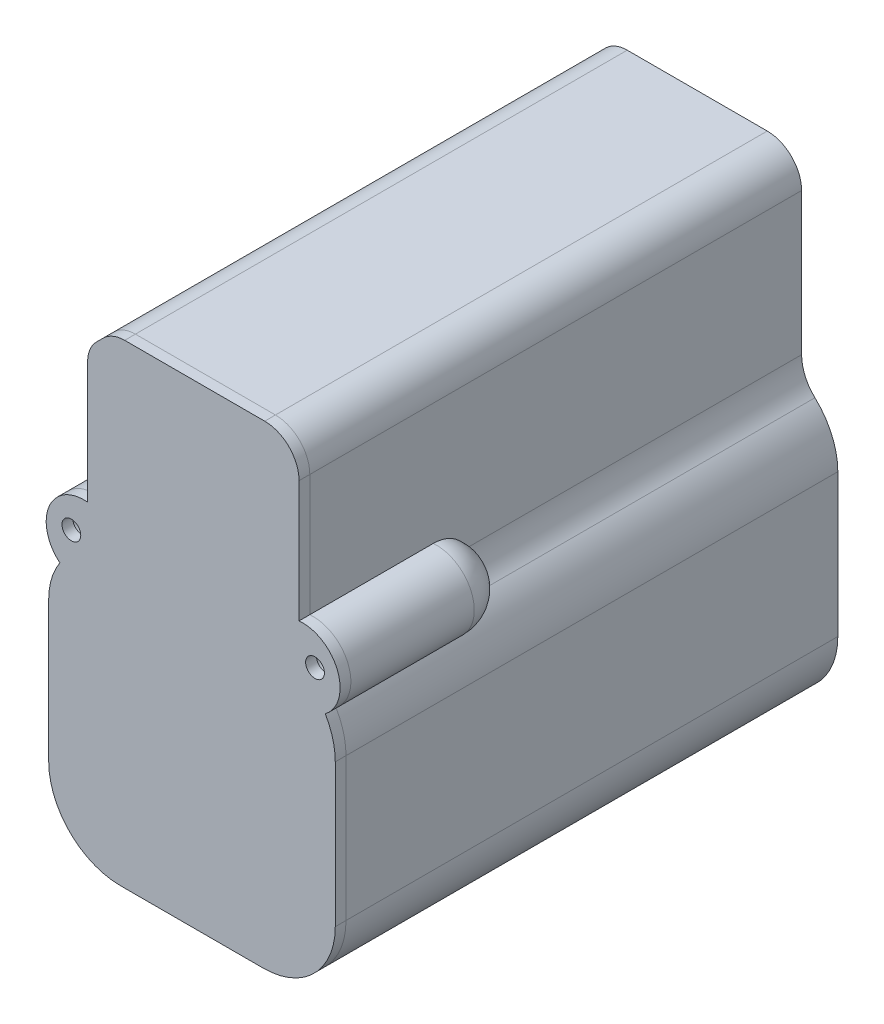
SolidWorks part; units mm, degrees
ref_plane "Front Plane" through (0, 0, 0) normal (0, 0, 1) x (1, 0, 0)
ref_plane "Top Plane" through (0, 0, 0) normal (0, 1, 0) x (1, 0, 0)
ref_plane "Right Plane" through (0, 0, 0) normal (1, 0, 0) x (0, 0, -1)
sketch "Sketch1" plane through (0, 0, 0) normal (0, 0, 1) x (1, 0, 0)
  line L1 (35, -50) -> (-35, -50)
  line L2 (35, -50) -> (35, 50)
  line L3 (35, 50) -> (-35, 50)
  line L4 (-35, -50) -> (-35, 50)
  line L5 (35, -50) -> (-35, 50) construction
  line L6 (35, 50) -> (-35, -50) construction
  point P0 (0, 0)
  dimension "D1" = 70
  dimension "D2" = 100
extrude "Boss-Extrude1" add sketch "Sketch1" along normal blind 2
sketch "Sketch2" plane through (0, 0, 0) normal (0, 0, -1) x (-1, 0, 0)
  line L0 (-17.2536, 39.8) -> (-17.2536, 13.2) construction
  line L1 (-13.0536, 9) -> (13.5464, 9) construction
  line L2 (17.7464, 13.2) -> (17.7464, 39.293) construction
  line L3 (16.7213, 41.7677) -> (15.5141, 42.9749) construction
  line L4 (13.0394, 44) -> (-13.0536, 44) construction
  line L5 (-17.2536, 39.8) -> (-17.2536, 13.3092) construction
  line L6 (-13.0536, 9) -> (13.5464, 9)
  line L7 (17.7464, 12.9384) -> (17.7464, 39.293) construction
  line L8 (16.7213, 41.7677) -> (15.5141, 42.9749) construction
  line L9 (13.0394, 44) -> (-13.0536, 44) construction
  line L10 (-24, -2.2) -> (-24, -28.8) construction
  line L11 (-12.8, -40) -> (13.8, -40) construction
  line L12 (25, -28.8) -> (25, -2.707) construction
  line L13 (21.9246, 4.7175) -> (20.7175, 5.9247) construction
  line L14 (13.2928, 9) -> (-12.8, 9) construction
  line L15 (-24, -2.2) -> (-24, -28.8) construction
  line L16 (-12.8, -40) -> (13.8, -40) construction
  line L17 (25, -28.8) -> (25, -2.707) construction
  line L18 (21.9246, 4.7175) -> (20.7175, 5.9247)
  line L19 (13.2928, 9) -> (-12.8, 9)
  line L20 (-17.4536, 39.8) -> (-17.4536, 13.3092)
  line L21 (13.0394, 44.2) -> (-13.0536, 44.2)
  line L22 (16.8627, 41.9092) -> (15.6556, 43.1163)
  line L23 (17.9464, 12.9384) -> (17.9464, 39.293)
  line L24 (25.2, -28.8) -> (25.2, -2.707)
  line L25 (-12.8, -40.2) -> (13.8, -40.2)
  line L26 (-24.2, -2.2) -> (-24.2, -28.8)
  line L27 (-26.2, -2.2) -> (-26.2, -28.8)
  line L28 (-12.8, -42.2) -> (13.8, -42.2)
  line L29 (27.2, -28.8) -> (27.2, -2.707)
  line L30 (19.9464, 12.9384) -> (19.9464, 39.293)
  line L31 (18.2769, 43.3234) -> (17.0698, 44.5306)
  line L32 (13.0393, 46.2) -> (-13.0536, 46.2)
  line L33 (-19.4536, 39.8) -> (-19.4536, 13.3092)
  arc A0 (-13.0536, 44) -> (-17.2536, 39.8) centre (-13.0536, 39.8) ccw construction
  arc A1 (-17.2536, 13.2) -> (-13.0536, 9) centre (-13.0536, 13.2) ccw construction
  arc A2 (13.5464, 9) -> (17.7464, 13.2) centre (13.5464, 13.2) ccw construction
  arc A3 (17.7464, 39.293) -> (16.7213, 41.7677) centre (14.2466, 39.293) ccw construction
  arc A4 (15.5141, 42.9749) -> (13.0394, 44) centre (13.0394, 40.5002) ccw construction
  arc A5 (-13.0536, 44) -> (-17.2536, 39.8) centre (-13.0536, 39.8) ccw construction
  arc A6 (-17.2536, 13.2) -> (-13.0536, 9) centre (-13.0536, 13.2) ccw
  arc A7 (13.5464, 9) -> (17.7464, 13.2) centre (13.5464, 13.2) ccw
  arc A8 (17.7464, 39.293) -> (16.7213, 41.7677) centre (14.2466, 39.293) ccw construction
  arc A9 (15.5141, 42.9749) -> (13.0394, 44) centre (13.0394, 40.5002) ccw construction
  arc A10 (-24, -28.8) -> (-12.8, -40) centre (-12.8, -28.8) ccw construction
  arc A11 (13.8, -40) -> (25, -28.8) centre (13.8, -28.8) ccw construction
  arc A12 (25, -2.707) -> (21.9246, 4.7175) centre (14.5002, -2.707) ccw construction
  arc A13 (20.7175, 5.9247) -> (13.2928, 9) centre (13.293, -1.4998) ccw construction
  arc A14 (-12.8, 9) -> (-24, -2.2) centre (-12.8, -2.2) ccw construction
  arc A15 (-24, -28.8) -> (-12.8, -40) centre (-12.8, -28.8) ccw construction
  arc A16 (13.8, -40) -> (25, -28.8) centre (13.8, -28.8) ccw construction
  arc A17 (25, -2.707) -> (21.2848, 5.3064) centre (14.5002, -2.707) ccw construction
  arc A18 (20.7175, 5.9247) -> (13.2928, 9) centre (13.293, -1.4998) ccw
  arc A19 (-20.4359, 5.9935) -> (-24, -2.2) centre (-12.8, -2.2) ccw construction
  arc A20 (21.2848, 5.3064) -> (17.7464, 12.9384) centre (27.7464, 12.9384) cw construction
  arc A21 (-20.4359, 5.9935) -> (-17.2536, 13.3092) centre (-27.2536, 13.3092) ccw construction
  arc A22 (-20.5722, 6.1398) -> (-17.4536, 13.3092) centre (-27.2536, 13.3092) ccw
  arc A23 (-13.0536, 44.2) -> (-17.4536, 39.8) centre (-13.0536, 39.8) ccw
  arc A24 (15.6556, 43.1163) -> (13.0394, 44.2) centre (13.0394, 40.5002) ccw
  arc A25 (17.9464, 39.293) -> (16.8627, 41.9092) centre (14.2466, 39.293) ccw
  arc A26 (21.414, 5.4591) -> (17.9464, 12.9384) centre (27.7464, 12.9384) cw
  arc A27 (25.2, -2.707) -> (21.414, 5.4591) centre (14.5002, -2.707) ccw
  arc A28 (13.8, -40.2) -> (25.2, -28.8) centre (13.8, -28.8) ccw
  arc A29 (-24.2, -28.8) -> (-12.8, -40.2) centre (-12.8, -28.8) ccw
  arc A30 (-20.5722, 6.1398) -> (-24.2, -2.2) centre (-12.8, -2.2) ccw
  arc A31 (-21.9358, 7.603) -> (-26.2, -2.2) centre (-12.8, -2.2) ccw
  arc A32 (-26.2, -28.8) -> (-12.8, -42.2) centre (-12.8, -28.8) ccw
  arc A33 (13.8, -42.2) -> (27.2, -28.8) centre (13.8, -28.8) ccw
  arc A34 (27.2, -2.707) -> (22.7063, 6.9855) centre (14.5002, -2.707) ccw
  arc A35 (22.7063, 6.9855) -> (19.9464, 12.9384) centre (27.7464, 12.9384) cw
  arc A36 (19.9464, 39.293) -> (18.2769, 43.3234) centre (14.2466, 39.293) ccw
  arc A37 (17.0698, 44.5306) -> (13.0393, 46.2) centre (13.0394, 40.5002) ccw
  arc A38 (-13.0536, 46.2) -> (-19.4536, 39.8) centre (-13.0536, 39.8) ccw
  arc A39 (-21.9358, 7.603) -> (-19.4536, 13.3092) centre (-27.2536, 13.3092) ccw
  line M23 (35, -50) -> (35, 50)
  line M24 (35, 50) -> (-35, 50)
  line M25 (-35, 50) -> (-35, -50)
  line M26 (-35, -50) -> (35, -50)
  dimension "D1" = 10
  dimension "D2" = 0.2
  dimension "D3" = 2
extrude "Cut-Extrude1" cut sketch "Sketch2" against normal up to next contours A31 A39 L33 A38 L32 A37 L31 A36 L30 A35 A34 L29 A33 L28 A32 L27 M26 M23 M24 M25 region at (0, -48.7793, 0)
sketch "Sketch3" plane through (0, 0, 0) normal (0, 0, -1) x (-1, 0, 0)
  line L0 (-19.4536, 39.8) -> (-19.4536, 13.3092) construction
  line L1 (-26.2, -2.2) -> (-26.2, -28.8) construction
  line L2 (-12.8, -42.2) -> (13.8, -42.2) construction
  line L3 (27.2, -28.8) -> (27.2, -2.707) construction
  line L4 (19.9464, 12.9384) -> (19.9464, 39.293) construction
  line L5 (18.2769, 43.3234) -> (17.0698, 44.5306) construction
  line L6 (13.0393, 46.2) -> (-13.0536, 46.2) construction
  line L7 (-19.4536, 39.8) -> (-19.4536, 13.3092)
  line L8 (-26.2, -2.2) -> (-26.2, -28.8)
  line L9 (-12.8, -42.2) -> (13.8, -42.2)
  line L10 (27.2, -28.8) -> (27.2, -2.707)
  line L11 (19.9464, 12.9384) -> (19.9464, 39.293)
  line L12 (18.2769, 43.3234) -> (17.0698, 44.5306)
  line L13 (13.0393, 46.2) -> (-13.0536, 46.2)
  arc A0 (-13.0536, 46.2) -> (-19.4536, 39.8) centre (-13.0536, 39.8) ccw construction
  arc A1 (-21.9358, 7.603) -> (-19.4536, 13.3092) centre (-27.2536, 13.3092) ccw construction
  arc A2 (-21.9358, 7.603) -> (-26.2, -2.2) centre (-12.8, -2.2) ccw construction
  arc A3 (-26.2, -28.8) -> (-12.8, -42.2) centre (-12.8, -28.8) ccw construction
  arc A4 (13.8, -42.2) -> (27.2, -28.8) centre (13.8, -28.8) ccw construction
  arc A5 (27.2, -2.707) -> (22.7063, 6.9855) centre (14.5002, -2.707) ccw construction
  arc A6 (19.9464, 12.9384) -> (22.7063, 6.9855) centre (27.7464, 12.9384) ccw construction
  arc A7 (19.9464, 39.293) -> (18.2769, 43.3234) centre (14.2466, 39.293) ccw construction
  arc A8 (17.0698, 44.5306) -> (13.0393, 46.2) centre (13.0394, 40.5002) ccw construction
  arc A9 (-13.0536, 46.2) -> (-19.4536, 39.8) centre (-13.0536, 39.8) ccw
  arc A10 (-21.9358, 7.603) -> (-19.4536, 13.3092) centre (-27.2536, 13.3092) ccw
  arc A11 (-21.9358, 7.603) -> (-26.2, -2.2) centre (-12.8, -2.2) ccw
  arc A12 (-26.2, -28.8) -> (-12.8, -42.2) centre (-12.8, -28.8) ccw
  arc A13 (13.8, -42.2) -> (27.2, -28.8) centre (13.8, -28.8) ccw
  arc A14 (27.2, -2.707) -> (22.7063, 6.9855) centre (14.5002, -2.707) ccw
  arc A15 (19.9464, 12.9384) -> (22.7063, 6.9855) centre (27.7464, 12.9384) ccw
  arc A16 (19.9464, 39.293) -> (18.2769, 43.3234) centre (14.2466, 39.293) ccw
  arc A17 (17.0698, 44.5306) -> (13.0393, 46.2) centre (13.0394, 40.5002) ccw
extrude "Extrude-Thin1" add sketch "Sketch3" against normal offset from surface (91.6373 mm away) 1.2 thin offset beyond the face yes thin type one direction reverse wall 2
sketch "Sketch4" plane through (0, 0, 91.6373) normal (0, 0, 1) x (1, 0, 0)
  line L0 (-19.9464, 12.9384) -> (-19.9464, 39.293) construction
  line L1 (-19.9464, 16.6201) -> (-25.1214, 4.2553) construction
  line L2 (-20.67, 9.6576) -> (-27.1272, 12.3601) construction
  line L10 (13.0536, 46.2) -> (-13.0394, 46.2)
  line L11 (-17.0698, 44.5306) -> (-18.277, 43.3233)
  line L12 (-19.9464, 39.293) -> (-19.9464, 12.9384)
  line L13 (-27.2, -2.707) -> (-27.2, -28.8)
  line L14 (-13.8, -42.2) -> (12.8, -42.2)
  line L15 (26.2, -28.8) -> (26.2, -2.2)
  line L16 (19.4536, 13.3092) -> (19.4536, 39.8)
  line L19 (-19.9464, 16.6201) -> (-19.9464, 12.9384)
  arc A0 (-19.9464, 16.6201) -> (-25.1214, 4.2553) centre (-20.67, 9.6576) ccw
  arc A1 (-22.7063, 6.9855) -> (-19.9464, 12.9384) centre (-27.7464, 12.9384) ccw construction
  arc A2 (-22.7063, 6.9855) -> (-27.2, -2.707) centre (-14.5002, -2.707) ccw construction
  arc A14 (19.4536, 39.8) -> (13.0536, 46.2) centre (13.0536, 39.8) ccw
  arc A15 (-13.0394, 46.2) -> (-17.0698, 44.5306) centre (-13.0394, 40.5002) ccw
  arc A16 (-18.277, 43.3233) -> (-19.9464, 39.293) centre (-14.2466, 39.293) ccw
  arc A17 (-22.7063, 6.9855) -> (-19.9464, 12.9384) centre (-27.7464, 12.9384) ccw
  arc A18 (-22.7063, 6.9855) -> (-27.2, -2.707) centre (-14.5002, -2.707) ccw
  arc A19 (-27.2, -28.8) -> (-13.8, -42.2) centre (-13.8, -28.8) ccw
  arc A20 (12.8, -42.2) -> (26.2, -28.8) centre (12.8, -28.8) ccw
  arc A21 (26.2, -2.2) -> (21.9358, 7.603) centre (12.8, -2.2) ccw
  arc A22 (19.4536, 13.3092) -> (21.9358, 7.603) centre (27.2536, 13.3092) ccw
  arc A26 (-22.7063, 6.9855) -> (-19.9464, 12.9384) centre (-27.7464, 12.9384) ccw
  arc A27 (-22.7063, 6.9855) -> (-25.1214, 4.2553) centre (-14.5002, -2.707) ccw
  dimension "D1" = 7
extrude "Boss-Extrude2" add sketch "Sketch4" against normal blind 30
sketch "Sketch5" plane through (0, 0, 91.6373) normal (0, 0, 1) x (1, 0, 0)
  line L0 (-19.9464, 16.6201) -> (-25.1214, 4.2553) construction
  line L1 (-18.8555, 8.8164) -> (-27.0906, 12.4462) construction
  arc A0 (-21.414, 5.4591) -> (-17.9464, 12.9384) centre (-27.7464, 12.9384) ccw construction
  arc A1 (-19.9464, 16.6201) -> (-25.1214, 4.2553) centre (-20.67, 9.6576) ccw construction
  circle A2 centre (-22.973, 10.6313) radius 2.3
  point P12 (-22.5339, 10.4377)
  point P15 (-22.973, 10.6313)
  dimension "D1" = 4.6
extrude "Cut-Extrude2" cut sketch "Sketch5" against normal blind 7
sketch "Sketch14" plane through (0, 0, 91.6373) normal (0, 0, 1) x (1, 0, 0)
  circle A0 centre (-22.973, 10.6313) radius 1.75
  dimension "D1" = 3.5
extrude "Cut-Extrude8" cut sketch "Sketch14" against normal blind 24
fillet "Fillet1" radius 7 1 edges at (-27.1272, 12.3601, 61.6373)
sketch "Sketch6" plane through (0, 0, 91.6373) normal (0, 0, 1) x (1, 0, 0)
  line L0 (19.4536, 39.8) -> (19.4536, 13.3092) construction
  line L8 (-19.9464, 39.293) -> (-19.9464, 16.6201)
  line L9 (-27.2, -2.707) -> (-27.2, -28.8)
  line L10 (-13.8, -42.2) -> (12.8, -42.2)
  line L11 (26.2, -28.8) -> (26.2, -2.2)
  line L12 (19.4536, 13.3092) -> (19.4536, 39.8)
  line L13 (13.0536, 46.2) -> (-13.0394, 46.2)
  line L14 (-17.0698, 44.5306) -> (-18.277, 43.3233)
  line L19 (19.4536, 13.3092) -> (19.4536, 17.1678)
  arc A0 (19.4536, 17.1678) -> (24.3333, 4.6222) centre (20.101, 10.1978) cw
  arc A1 (19.4536, 13.3092) -> (21.9358, 7.603) centre (27.2536, 13.3092) ccw construction
  arc A2 (26.2, -2.2) -> (21.9358, 7.603) centre (12.8, -2.2) ccw construction
  arc A12 (-19.9464, 16.6201) -> (-25.1214, 4.2553) centre (-20.67, 9.6576) ccw
  arc A13 (-25.1214, 4.2553) -> (-27.2, -2.707) centre (-14.5002, -2.707) ccw
  arc A14 (-27.2, -28.8) -> (-13.8, -42.2) centre (-13.8, -28.8) ccw
  arc A15 (12.8, -42.2) -> (26.2, -28.8) centre (12.8, -28.8) ccw
  arc A16 (26.2, -2.2) -> (21.9358, 7.603) centre (12.8, -2.2) ccw
  arc A17 (19.4536, 13.3092) -> (21.9358, 7.603) centre (27.2536, 13.3092) ccw
  arc A18 (19.4536, 39.8) -> (13.0536, 46.2) centre (13.0536, 39.8) ccw
  arc A19 (-13.0394, 46.2) -> (-17.0698, 44.5306) centre (-13.0394, 40.5002) ccw
  arc A20 (-18.277, 43.3233) -> (-19.9464, 39.293) centre (-14.2466, 39.293) ccw
  arc A25 (24.3333, 4.6222) -> (21.9358, 7.603) centre (12.8, -2.2) ccw
  arc A26 (19.4536, 13.3092) -> (21.9358, 7.603) centre (27.2536, 13.3092) ccw
  dimension "D1" = 7
extrude "Boss-Extrude3" add sketch "Sketch6" against normal blind 30
fillet "Fillet3" radius 7 1 edges at (26.6249, 12.7353, 61.6373)
sketch "Sketch7" plane through (0, 0, 91.6373) normal (0, 0, 1) x (1, 0, 0)
  line L0 (19.4536, 17.1678) -> (24.3333, 4.6222) construction
  line L1 (18.267, 9.4) -> (26.5873, 12.83) construction
  arc A0 (17.4536, 13.3092) -> (20.5722, 6.1398) centre (27.2536, 13.3092) ccw construction
  arc A1 (24.3333, 4.6222) -> (19.4536, 17.1678) centre (20.101, 10.1978) ccw construction
  circle A2 centre (22.4271, 11.115) radius 2.3
  point P12 (21.8934, 10.895)
  point P16 (22.4271, 11.115)
  dimension "D1" = 4.6
extrude "Cut-Extrude3" cut sketch "Sketch7" against normal blind 7
sketch "Sketch15" plane through (0, 0, 91.6373) normal (0, 0, 1) x (1, 0, 0)
  circle A0 centre (22.4271, 11.115) radius 1.75
  dimension "D1" = 3.5
extrude "Cut-Extrude9" cut sketch "Sketch15" against normal blind 24
sketch "Sketch9" plane through (0, 0, 0) normal (0, 0, -1) x (-1, 0, 0)
  line L28 (13.7464, 15) -> (13.7464, 38)
  line L29 (11.7464, 40) -> (-11.2536, 40)
  line L30 (-13.2536, 38) -> (-13.2536, 15)
  line L31 (-11.2536, 13) -> (11.7464, 13)
  line L32 (13.7464, 15) -> (13.7464, 38)
  line L33 (11.7464, 40) -> (-11.2536, 40)
  line L34 (-13.2536, 38) -> (-13.2536, 15)
  line L35 (-11.2536, 13) -> (11.7464, 13)
  line L52 (-12.8, -36) -> (13.8, -36)
  line L53 (21, -28.8) -> (21, -2.707)
  line L54 (19.0962, 1.8891) -> (17.889, 3.0962)
  line L55 (13.2929, 5) -> (-12.8, 5)
  line L56 (-20, -2.2) -> (-20, -28.8)
  line L57 (-12.8, -36) -> (13.8, -36)
  line L58 (21, -28.8) -> (21, -2.707)
  line L59 (19.0962, 1.8891) -> (17.889, 3.0962)
  line L60 (13.2929, 5) -> (-12.8, 5)
  line L61 (-20, -2.2) -> (-20, -28.8)
  arc A28 (11.7464, 13) -> (13.7464, 15) centre (11.7464, 15) ccw
  arc A29 (13.7464, 38) -> (11.7464, 40) centre (11.7464, 38) ccw
  arc A30 (-11.2536, 40) -> (-13.2536, 38) centre (-11.2536, 38) ccw
  arc A31 (-13.2536, 15) -> (-11.2536, 13) centre (-11.2536, 15) ccw
  arc A32 (11.7464, 13) -> (13.7464, 15) centre (11.7464, 15) ccw
  arc A33 (13.7464, 38) -> (11.7464, 40) centre (11.7464, 38) ccw
  arc A34 (-11.2536, 40) -> (-13.2536, 38) centre (-11.2536, 38) ccw
  arc A35 (-13.2536, 15) -> (-11.2536, 13) centre (-11.2536, 15) ccw
  arc A52 (-20, -28.8) -> (-12.8, -36) centre (-12.8, -28.8) ccw
  arc A53 (13.8, -36) -> (21, -28.8) centre (13.8, -28.8) ccw
  arc A54 (21, -2.707) -> (19.0962, 1.8891) centre (14.5002, -2.707) ccw
  arc A55 (17.889, 3.0962) -> (13.2929, 5) centre (13.293, -1.4998) ccw
  arc A56 (-12.8, 5) -> (-20, -2.2) centre (-12.8, -2.2) ccw
  arc A57 (-20, -28.8) -> (-12.8, -36) centre (-12.8, -28.8) ccw
  arc A58 (13.8, -36) -> (21, -28.8) centre (13.8, -28.8) ccw
  arc A59 (21, -2.707) -> (19.0962, 1.8891) centre (14.5002, -2.707) ccw
  arc A60 (17.889, 3.0962) -> (13.2929, 5) centre (13.293, -1.4998) ccw
  arc A61 (-12.8, 5) -> (-20, -2.2) centre (-12.8, -2.2) ccw
  dimension "D1" = 1
  dimension "D2" = 1
extrude "Cut-Extrude4" cut sketch "Sketch9" against normal up to next
sketch "Sketch10" plane through (0, 0, 91.6373) normal (0, 0, 1) x (1, 0, 0)
  line L0 (26.2, -2.2) -> (26.2, -28.8) construction
  line L1 (12.8, -42.2) -> (-13.8, -42.2) construction
  line L2 (-27.2, -28.8) -> (-27.2, -2.707) construction
  line L3 (19.4536, 39.8) -> (19.4536, 17.1678) construction
  line L4 (-13.0393, 46.2) -> (13.0536, 46.2) construction
  line L5 (-18.2769, 43.3234) -> (-17.0698, 44.5306) construction
  line L6 (-19.9464, 16.6201) -> (-19.9464, 39.293) construction
  line L7 (26.2, -2.2) -> (26.2, -28.8)
  line L8 (12.8, -42.2) -> (-13.8, -42.2)
  line L9 (-27.2, -28.8) -> (-27.2, -2.707)
  line L10 (19.4536, 39.8) -> (19.4536, 17.1678)
  line L11 (-13.0393, 46.2) -> (13.0536, 46.2)
  line L12 (-18.2769, 43.3234) -> (-17.0698, 44.5306)
  line L13 (-19.9464, 16.6201) -> (-19.9464, 39.293)
  arc A0 (-25.1214, 4.2553) -> (-27.2, -2.707) centre (-14.5002, -2.707) ccw construction
  arc A1 (26.2, -2.2) -> (24.3333, 4.6222) centre (12.8, -2.2) ccw construction
  arc A2 (12.8, -42.2) -> (26.2, -28.8) centre (12.8, -28.8) ccw construction
  arc A3 (-27.2, -28.8) -> (-13.8, -42.2) centre (-13.8, -28.8) ccw construction
  arc A4 (24.3333, 4.6222) -> (19.4536, 17.1678) centre (20.101, 10.1978) ccw construction
  arc A5 (-19.9464, 16.6201) -> (-25.1214, 4.2553) centre (-20.67, 9.6576) ccw construction
  arc A6 (19.4536, 39.8) -> (13.0536, 46.2) centre (13.0536, 39.8) ccw construction
  arc A7 (-13.0393, 46.2) -> (-17.0698, 44.5306) centre (-13.0394, 40.5002) ccw construction
  arc A8 (-18.2769, 43.3234) -> (-19.9464, 39.293) centre (-14.2466, 39.293) ccw construction
  arc A9 (-25.1214, 4.2553) -> (-27.2, -2.707) centre (-14.5002, -2.707) ccw
  arc A10 (26.2, -2.2) -> (24.3333, 4.6222) centre (12.8, -2.2) ccw
  arc A11 (12.8, -42.2) -> (26.2, -28.8) centre (12.8, -28.8) ccw
  arc A12 (-27.2, -28.8) -> (-13.8, -42.2) centre (-13.8, -28.8) ccw
  arc A13 (24.3333, 4.6222) -> (19.4536, 17.1678) centre (20.101, 10.1978) ccw
  arc A14 (-19.9464, 16.6201) -> (-25.1214, 4.2553) centre (-20.67, 9.6576) ccw
  arc A15 (19.4536, 39.8) -> (13.0536, 46.2) centre (13.0536, 39.8) ccw
  arc A16 (-13.0393, 46.2) -> (-17.0698, 44.5306) centre (-13.0394, 40.5002) ccw
  arc A17 (-18.2769, 43.3234) -> (-19.9464, 39.293) centre (-14.2466, 39.293) ccw
extrude "Boss-Extrude4" add sketch "Sketch10" along normal blind 2 separate body
sketch "Sketch11" plane through (0, 0, 93.6373) normal (0, 0, 1) x (1, 0, 0)
  circle A0 centre (-22.973, 10.6313) radius 1.75
  circle A1 centre (22.4271, 11.115) radius 1.75
  dimension "D1" = 3.5
  dimension "D2" = 3.5
extrude "Cut-Extrude5" cut sketch "Sketch11" against normal up to next (2 mm away)
sketch "Sketch12" plane through (-19.9464, 0, 0) normal (-1, 0, 0) x (0, 0, 1)
  line L0 (30.2675, 17.7465) -> (39.2675, 17.7465) construction
  line L1 (39.2675, 17.7465) -> (39.2675, 34.7465) construction
  line L2 (39.2675, 34.7465) -> (30.2675, 34.7465) construction
  line L3 (30.2675, 34.7465) -> (30.2675, 17.7465) construction
  line L4 (30.2675, 17.7465) -> (39.2675, 17.7465) construction
  line L5 (39.2675, 17.7465) -> (39.2675, 34.7465) construction
  line L6 (39.2675, 34.7465) -> (30.2675, 34.7465) construction
  line L7 (30.2675, 34.7465) -> (30.2675, 17.7465) construction
  line L8 (30.2675, 16.7465) -> (39.2675, 16.7465)
  line L9 (40.2675, 17.7465) -> (40.2675, 34.7465)
  line L10 (39.2675, 35.7465) -> (30.2675, 35.7465)
  line L11 (29.2675, 34.7465) -> (29.2675, 17.7465)
  line L12 (29.2675, 35.7465) -> (29.2675, 16.7465) construction
  line L13 (29.2675, 16.7465) -> (40.2675, 16.7465) construction
  line L14 (40.2675, 16.7465) -> (40.2675, 35.7465) construction
  line L15 (40.2675, 35.7465) -> (29.2675, 35.7465) construction
  arc A0 (29.2675, 17.7465) -> (30.2675, 16.7465) centre (30.2675, 17.7465) ccw
  arc A1 (40.2675, 17.7465) -> (39.2675, 16.7465) centre (39.2675, 17.7465) cw
  arc A2 (40.2675, 34.7465) -> (39.2675, 35.7465) centre (39.2675, 34.7465) ccw
  arc A3 (29.2675, 34.7465) -> (30.2675, 35.7465) centre (30.2675, 34.7465) cw
  dimension "D2" = 1
  dimension "D1" = 1
extrude "Cut-Extrude6" cut sketch "Sketch12" against normal up to next (2 mm away)
sketch "Sketch13" plane through (-27.2, 0, 0) normal (-1, 0, 0) x (0, 0, 1)
  line L0 (78.947, -24) -> (87.8341, -24) construction
  line L1 (87.8341, -24) -> (87.947, -7) construction
  line L2 (78.947, -7) -> (78.947, -24) construction
  line L3 (87.947, -7) -> (78.947, -7) construction
  line L4 (78.947, -24) -> (87.8341, -24) construction
  line L5 (87.8341, -24) -> (87.947, -7) construction
  line L6 (78.947, -7) -> (78.947, -24) construction
  line L7 (87.947, -7) -> (78.947, -7) construction
  line L8 (78.947, -25) -> (87.8341, -25)
  line L9 (88.8341, -24.0066) -> (88.9469, -7.0066)
  line L10 (87.947, -6) -> (78.947, -6)
  line L11 (77.947, -7) -> (77.947, -24)
  line L12 (77.947, -6) -> (77.947, -25) construction
  line L13 (77.947, -25) -> (88.8275, -25) construction
  line L14 (88.8275, -25) -> (88.9536, -6) construction
  line L15 (88.9536, -6) -> (77.947, -6) construction
  arc A0 (77.947, -24) -> (78.947, -25) centre (78.947, -24) ccw
  arc A1 (88.8341, -24.0066) -> (87.8341, -25) centre (87.8341, -24) cw
  arc A2 (88.9469, -7.0066) -> (87.947, -6) centre (87.947, -7) ccw
  arc A3 (77.947, -7) -> (78.947, -6) centre (78.947, -7) cw
  dimension "D2" = 1
  dimension "D1" = 1
extrude "Cut-Extrude7" cut sketch "Sketch13" against normal up to next (2 mm away)
sketch "Sketch16" plane through (0, 0, 91.6373) normal (0, 0, -1) x (-1, 0, 0)
  line L14 (-17.2536, 39.8) -> (-17.2536, 13.3092)
  line L15 (-24, -2.2) -> (-24, -28.8)
  line L16 (-12.8, -40) -> (13.8, -40)
  line L17 (25, -28.8) -> (25, -2.707)
  line L18 (17.7464, 12.9384) -> (17.7464, 39.293)
  line L19 (16.7213, 41.7677) -> (15.5141, 42.9749)
  line L20 (13.0393, 44) -> (-13.0536, 44)
  line L21 (-17.2536, 39.8) -> (-17.2536, 13.3092)
  line L22 (-24, -2.2) -> (-24, -28.8)
  line L23 (-12.8, -40) -> (13.8, -40)
  line L24 (25, -28.8) -> (25, -2.707)
  line L25 (17.7464, 12.9384) -> (17.7464, 39.293)
  line L26 (16.7213, 41.7677) -> (15.5141, 42.9749)
  line L27 (13.0393, 44) -> (-13.0536, 44)
  arc A18 (-13.0536, 44) -> (-17.2536, 39.8) centre (-13.0536, 39.8) ccw
  arc A19 (-20.4359, 5.9935) -> (-17.2536, 13.3092) centre (-27.2536, 13.3092) ccw
  arc A20 (-20.4359, 5.9935) -> (-24, -2.2) centre (-12.8, -2.2) ccw
  arc A21 (-24, -28.8) -> (-12.8, -40) centre (-12.8, -28.8) ccw
  arc A22 (13.8, -40) -> (25, -28.8) centre (13.8, -28.8) ccw
  arc A23 (25, -2.707) -> (21.2848, 5.3064) centre (14.5002, -2.707) ccw
  arc A24 (17.7464, 12.9384) -> (21.2848, 5.3064) centre (27.7464, 12.9384) ccw
  arc A25 (17.7464, 39.293) -> (16.7213, 41.7677) centre (14.2466, 39.293) ccw
  arc A26 (15.5141, 42.9749) -> (13.0393, 44) centre (13.0394, 40.5002) ccw
  arc A27 (-13.0536, 44) -> (-17.2536, 39.8) centre (-13.0536, 39.8) ccw
  arc A28 (-20.4359, 5.9935) -> (-17.2536, 13.3092) centre (-27.2536, 13.3092) ccw
  arc A29 (-20.4359, 5.9935) -> (-24, -2.2) centre (-12.8, -2.2) ccw
  arc A30 (-24, -28.8) -> (-12.8, -40) centre (-12.8, -28.8) ccw
  arc A31 (13.8, -40) -> (25, -28.8) centre (13.8, -28.8) ccw
  arc A32 (25, -2.707) -> (21.2848, 5.3064) centre (14.5002, -2.707) ccw
  arc A33 (17.7464, 12.9384) -> (21.2848, 5.3064) centre (27.7464, 12.9384) ccw
  arc A34 (17.7464, 39.293) -> (16.7213, 41.7677) centre (14.2466, 39.293) ccw
  arc A35 (15.5141, 42.9749) -> (13.0393, 44) centre (13.0394, 40.5002) ccw
  dimension "D1" = 0.2
extrude "Extrude-Thin2" add sketch "Sketch16" along normal blind 1 thin thin type one direction reverse wall 1
sketch "Sketch17" plane through (0, 0, 91.6373) normal (0, 0, -1) x (-1, 0, 0)
  line L2 (-17.2536, 13.2) -> (-17.2536, 39.8) construction
  line L3 (-13.0536, 44) -> (13.0394, 44) construction
  circle A0 centre (-0.0071, 26.5) radius 3
  point P4 (-17.2536, 26.5)
  point P7 (-0.0071, 44)
  dimension "D1" = 6
  dimension "D2" = 0
  dimension "D3" = 0
extrude "Boss-Extrude5" add sketch "Sketch17" along normal offset from surface (49.8373 mm away) 0.2
sketch "Sketch18" plane through (0, 0, 41.8) normal (0, 0, -1) x (-1, 0, 0)
  circle A0 centre (-0.0071, 26.5) radius 2
  dimension "D1" = 4
extrude "Cut-Extrude10" cut sketch "Sketch18" against normal offset from surface (47.8373 mm away) 2 up to face at (3.0071, 26.5, 91.6373)
equation "\"base_thickness\"= 2"
equation "\"front_thickness\"= 2"
equation "\"back_offset\"= 1.5"
equation "\"base_side_offset\"= 1"
equation "\"hole_inner_radius\"=2"
equation "\"snap_fit_thickness\"= 2"
equation "\"hole_outer_radius\"= 6"
equation "\"base_enclosure_camera_gap\"= 1"
equation "\"camera_front_enclosure_gap\"= 4"
equation "\"usb_hole_width\"= 9"
equation "\"usb_hole_length\"= 17"
equation "\"snap_fit_width\"= 6"
equation "\"snap_fit_base_length\"= 5.5"
equation "\"snap_fit_front_length\"= 7"
equation "\"snap_fit_height\"= 0.9"
equation "\"snap_fit_front_length_wide_cam\"= 8"
equation "\"D1@Boss-Extrude1\"=\"base_thickness\""
equation "\"outer_enclosure_offset\"= 0.2"
equation "\"D2@Sketch2\"=\"outer_enclosure_offset\""
equation "\"D3@Sketch2\"=\"base_thickness\""
equation "\"D5@Extrude-Thin1\"=\"base_thickness\""
equation "\"D1@Extrude-Thin1\"=\"outer_enclosure_offset\"+1"
equation "\"D1@Sketch5\"=\"thread_insert_d_outer_enclosure\"-0.4"
equation "\"D1@Sketch7\"=\"thread_insert_d_outer_enclosure\"-0.4"
equation "\"D1@Boss-Extrude4\"=\"base_thickness\""
equation "\"thread_insert_d_outer_enclosure\"= 5'outer inclosure thread insert diameter"
equation "\"screw_d_outer_enclousre\"= 3.5'diameter of screw outer enclosure"
equation "\"D1@Sketch4\"=\"thread_insert_d_outer_enclosure\"+2"
equation "\"D1@Fillet1\"=\"thread_insert_d_outer_enclosure\"+2"
equation "\"D1@Sketch6\"=\"thread_insert_d_outer_enclosure\"+2"
equation "\"D1@Fillet3\"=\"thread_insert_d_outer_enclosure\"+2"
equation "\"thread_insert_h_outer_enclosure\"= 5'outer enclosure thread insert height"
equation "\"screw_h_outer_enclosure\"= 23'outer_enclosure_screw_height"
equation "\"D1@Cut-Extrude2\"=\"thread_insert_h_outer_enclosure\"+2"
equation "\"D1@Sketch14\"=\"screw_d_outer_enclousre\""
equation "\"D1@Cut-Extrude8\"=\"screw_h_outer_enclosure\"+1"
equation "\"D1@Cut-Extrude3\"=\"thread_insert_h_outer_enclosure\"+2"
equation "\"D1@Sketch15\"=\"screw_d_outer_enclousre\""
equation "\"D1@Cut-Extrude9\"=\"screw_h_outer_enclosure\"+1"
equation "\"D1@Sketch11\"=\"screw_d_outer_enclousre\""
equation "\"D2@Sketch11\"=\"screw_d_outer_enclousre\""
